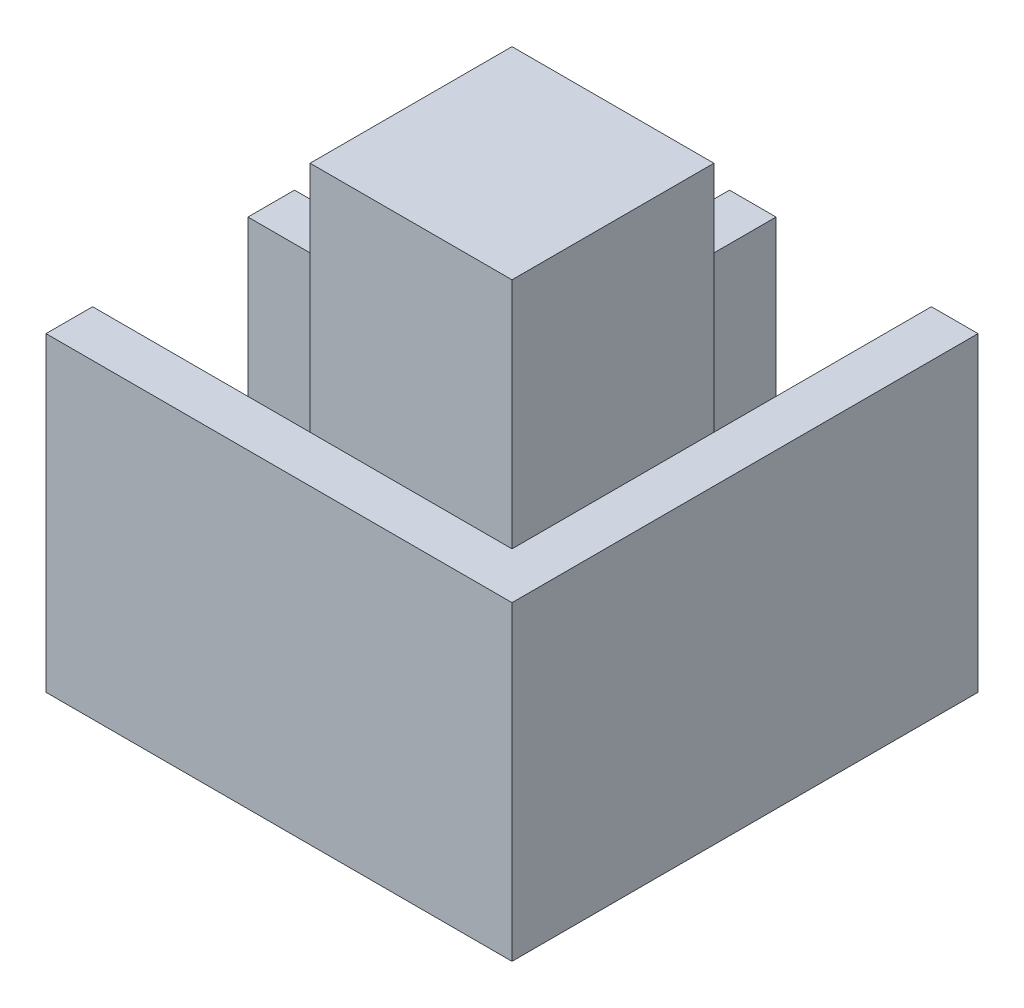
SolidWorks part; units mm, degrees
ref_plane "Front Plane" through (0, 0, 0) normal (0, 0, 1) x (1, 0, 0)
ref_plane "Top Plane" through (0, 0, 0) normal (0, 1, 0) x (1, 0, 0)
ref_plane "Right Plane" through (0, 0, 0) normal (1, 0, 0) x (0, 0, -1)
sketch "Sketch1" plane through (0, 0, 0) normal (0, 1, 0) x (1, 0, 0)
  line L0 (12, -12) -> (12, 12)
  line L1 (-15, -15) -> (15, -15)
  line L2 (-15, -15) -> (-15, 15)
  line L3 (-15, 15) -> (15, 15)
  line L4 (15, -15) -> (15, 15)
  line L5 (-15, -15) -> (15, 15) construction
  line L6 (-15, 15) -> (15, -15) construction
  line L9 (-12, -12) -> (12, -12)
  line L10 (-12, -12) -> (-12, 12) construction
  line L11 (-12, 12) -> (12, 12) construction
  line L12 (-1, -12) -> (-1, 15)
  line L13 (12, -12) -> (-15, -12)
  line L14 (12, -12) -> (12, -2)
  line L15 (12, -2) -> (-15, -2)
  line L16 (-15, -12) -> (-15, -2)
  line L17 (12, -12) -> (2, -12)
  line L18 (12, -12) -> (12, 15)
  line L19 (12, 15) -> (2, 15)
  line L20 (2, -12) -> (2, 15)
  line L21 (12, 1) -> (-15, 1)
  point P0 (0, 0)
  dimension "D1" = 30
  dimension "D2" = 30
  dimension "D4" = 10
  dimension "D5" = 10
  dimension "D3" = 3
  dimension "D6" = 3
  dimension "D7" = 3
extrude "Boss-Extrude1" add sketch "Sketch1" against normal blind 20 contours L15 L20 L3 L2 | L9 L20 L15 L2 L13 | L2 L1 L4 L3 region at (-8, 0, 7) region at (-8, 0, -8)
extrude "Cut-Extrude1" cut sketch "Sketch1<6>" against normal blind 15 contours L21 L18 L3 L20 | L12 L15 L2 L13 L9 | L21 L12 L3 L2 region at (7, 0, -8) region at (-8, 0, 7) region at (-8, 0, -8)
sketch "Sketch1<6>" plane through (0, 0, 0) normal (0, 1, 0) x (1, 0, 0) same geometry as "Sketch1"
extrude "Boss-Extrude2" add sketch "Sketch1<7>" along normal blind 15 contours L20 L13 L0 L15 | L0 L21 L20 L15 | L9 L20 L15 L12 | L20 L21 L12 L15 region at (7, 0, 7) region at (7, 0, 0.5) region at (0.5, 0, 7) region at (0.5, 0, 0.5)
sketch "Sketch1<7>" plane through (0, 0, 0) normal (0, 1, 0) x (1, 0, 0) same geometry as "Sketch1"
